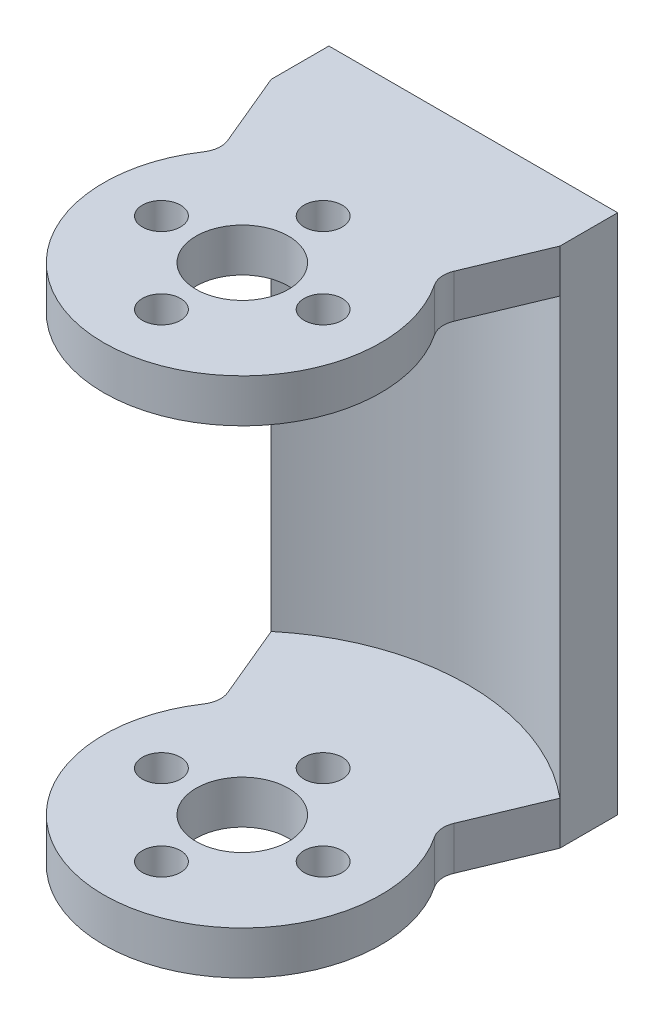
SolidWorks part; units mm, degrees
ref_plane "Front Plane" through (0, 0, 0) normal (0, 0, 1) x (1, 0, 0)
ref_plane "Top Plane" through (0, 0, 0) normal (0, 1, 0) x (1, 0, 0)
ref_plane "Right Plane" through (0, 0, 0) normal (1, 0, 0) x (0, 0, -1)
sketch "Sketch1" plane through (0, 0, 0) normal (0, 1, 0) x (1, 0, 0)
  line L2 (-12.5, 15) -> (-12.5, 20)
  line L3 (-12.5, 20) -> (12.5, 20)
  line L4 (12.5, 15) -> (12.5, 20)
  line L5 (-12.5, 15) -> (-9.3675, 7.5)
  line L6 (9.3675, 7.5) -> (12.5, 15)
  circle A3 centre (0, 0) radius 4
  arc A4 (-9.3675, 7.5) -> (9.3675, 7.5) centre (0, 0) ccw
  point P12 (-12.5, 0)
  point P13 (0, 20)
  dimension "D3" = 0
  dimension "D4" = 20
  dimension "D6" = 8
  dimension "D2" = 12
  dimension "D1" = 25
  dimension "D5" = 5
  dimension "D7" = 12.5
extrude "Boss-Extrude1" add sketch "Sketch1" along normal blind 45.15
sketch "Sketch2" plane through (-12.5, 0, 0) normal (-1, 0, 0) x (0, 0, 1)
  line L1 (25, 3.75) -> (-15, 3.75)
  line L2 (25, 3.75) -> (25, 41.4)
  line L3 (25, 41.4) -> (-15, 41.4)
  line L4 (-15, 3.75) -> (-15, 41.4)
  line L5 (-20, 45.15) -> (-20, 0) construction
  point P6 (-20, 22.575)
  point P7 (25, 22.575)
  dimension "D1" = 37.65
  dimension "D2" = 5
  dimension "D3" = 45
extrude "Cut-Extrude1" cut sketch "Sketch2" against normal through all
ref_plane "B mid plane" through (0, 22.575, 0) normal (0, -1, 0) x (-1, 0, 0)
sketch "Sketch3" plane through (0, 45.15, 0) normal (0, 1, 0) x (1, 0, 0)
  circle A0 centre (0, 7) radius 1.65
  circle A1 centre (0, 0) radius 4 construction
  dimension "D1" = 3.3
  dimension "D2" = 7
  dimension "D3" = 0
extrude "Cut-Extrude2" cut sketch "Sketch3" against normal through all
ref_axis "Axis1" through (0, 45.15, 0) along (0, -1, 0)
pattern_circular "CirPattern1" count 4 over 360 about axis through (0, 45.15, 0) along (0, -1, 0) of "Cut-Extrude2"
fillet "Fillet1" radius 2 4 edges at (9.3675, 43.275, -7.5) (9.3675, 1.875, -7.5) (-9.3675, 43.275, -7.5) (-9.3675, 1.875, -7.5)
sketch "Sketch4" plane through (0, 3.75, 0) normal (0, 1, 0) x (1, 0, 0)
  line L0 (9.8015, 8.5391) -> (12.5, 15) construction
  line L1 (-12.5, 15) -> (12.5, 15)
  arc A0 (-12.5, 15) -> (12.5, 15) centre (0, 0) cw
  dimension "D1" = 19.5256
extrude "Cut-Extrude4" cut sketch "Sketch4" along normal up to surface (37.65 mm away) up to face at (7, 41.4, 1.65)
